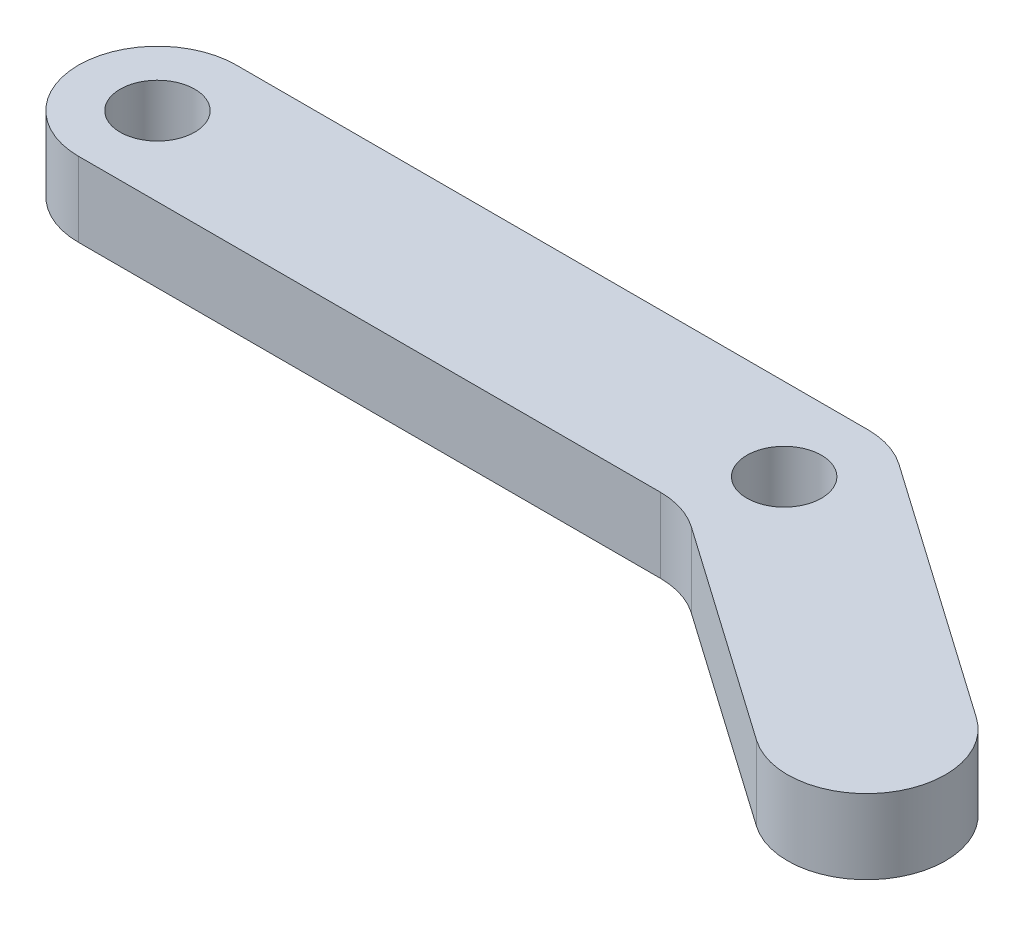
SolidWorks part; units mm, degrees
ref_plane "Front Plane" through (0, 0, 0) normal (0, 0, 1) x (1, 0, 0)
ref_plane "Top Plane" through (0, 0, 0) normal (0, 1, 0) x (1, 0, 0)
ref_plane "Right Plane" through (0, 0, 0) normal (1, 0, 0) x (0, 0, -1)
sketch "Sketch1" plane through (0, 0, 0) normal (0, 1, 0) x (1, 0, 0)
  line L0 (0, 0) -> (25.4, 0) construction
  line L1 (25.4, 0) -> (35.8032, -7.2844) construction
  line L2 (0, -3.175) -> (23.3979, -3.175)
  line L3 (25.219, -3.7492) -> (33.9821, -9.8852)
  line L4 (0, 3.175) -> (25.4, 3.175)
  line L5 (27.2211, 2.6008) -> (37.6243, -4.6836)
  line L6 (0, -3.175) -> (24.3989, -3.175) construction
  line L7 (24.3989, -3.175) -> (33.9821, -9.8852) construction
  line L8 (0, 3.175) -> (26.4011, 3.175) construction
  line L9 (26.4011, 3.175) -> (37.6243, -4.6836) construction
  line L10 (24.3526, -3.3219) -> (26.3547, 3.0281) construction
  arc A0 (0, -3.175) -> (0, 3.175) centre (0, 0) cw
  arc A1 (33.9821, -9.8852) -> (37.6243, -4.6836) centre (35.8032, -7.2844) ccw
  arc A2 (23.3979, -3.175) -> (25.219, -3.7492) centre (23.3979, -6.35) cw
  arc A3 (25.4, 3.175) -> (27.2211, 2.6008) centre (25.4, 0) cw
  circle A4 centre (25.3537, -0.1469) radius 1.5
  circle A5 centre (0, 0) radius 1.5
  dimension "D6" = 3
  dimension "D1" = 12.7
  dimension "D2" = 25.4
  dimension "D5" = 145
  dimension "D3" = 3.175
  dimension "D4" = 3.175
extrude "Boss-Extrude1" add sketch "Sketch1" along normal blind 3
